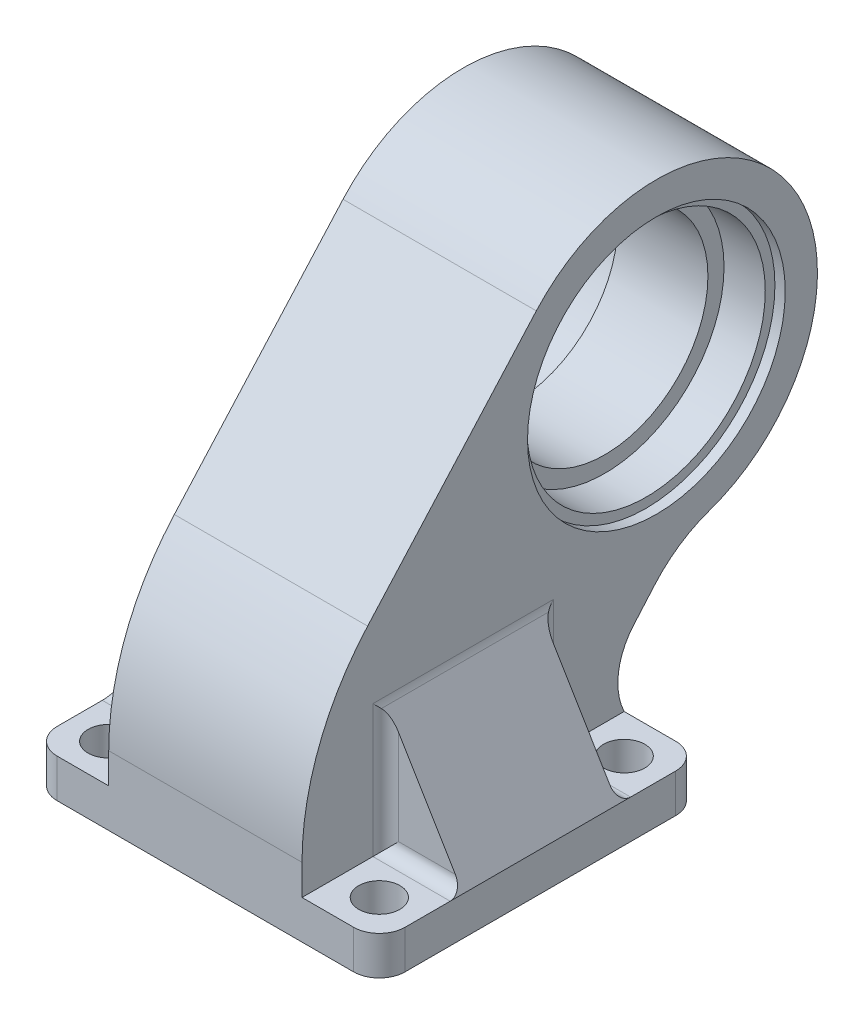
SolidWorks part; units mm, degrees
ref_plane "前视基准面" through (0, 0, 0) normal (0, 0, 1) x (1, 0, 0)
ref_plane "上视基准面" through (0, 0, 0) normal (0, 1, 0) x (1, 0, 0)
ref_plane "右视基准面" through (0, 0, 0) normal (1, 0, 0) x (0, 0, -1)
sketch "草图1" plane through (0, 0, 0) normal (0, 1, 0) x (1, 0, 0)
  line L1 (-13.5, -12.5) -> (13.5, -12.5)
  line L2 (-13.5, -12.5) -> (-13.5, 12.5)
  line L3 (-13.5, 12.5) -> (13.5, 12.5)
  line L4 (13.5, -12.5) -> (13.5, 12.5)
  line L5 (-13.5, -12.5) -> (13.5, 12.5) construction
  line L6 (-13.5, 12.5) -> (13.5, -12.5) construction
  point P0 (0, 0)
  dimension "D1" = 27
  dimension "D2" = 25
extrude "凸台-拉伸1" add sketch "草图1" along normal blind 3
sketch "草图2" plane through (0, 0, 0) normal (0, -1, 0) x (1, 0, 0)
  line L0 (0, 11.2561) -> (0, -9.0083) construction
  line L1 (-12.0564, 0) -> (11.3753, 0) construction
  circle A0 centre (-10.5, 9.5) radius 1.6
  circle A1 centre (-10.5, -9.5) radius 1.6
  circle A2 centre (10.5, -9.5) radius 1.6
  circle A3 centre (10.5, 9.5) radius 1.6
  dimension "D1" = 3.2
  dimension "D2" = 21
  dimension "D3" = 19
extrude "切除-拉伸1" cut sketch "草图2" against normal up to next
sketch "草图4" plane through (0, 0, 0) normal (1, 0, 0) x (0, 0, -1)
  line L0 (0, 0) -> (0, 12.2864) construction
  line L2 (-12.5, 3) -> (-12.5, 13)
  line L3 (-12.5, 13) -> (5.6822, 33.3324)
  line L4 (-12.5, 0) -> (12.5, 0) construction
  line L5 (12.5, 3) -> (24.4547, 16.8233)
  line L6 (-12.5, 3) -> (12.5, 3)
  circle A0 centre (15, 25) radius 12.5
  dimension "D1" = 25
  dimension "D3" = 25
  dimension "D2" = 15
  dimension "D4" = 10
extrude "圆孔位置" add sketch "草图4" along normal mid plane 15 contours A0 L3 L2 L6 L5 | A0 L2 region at (0, 11.7442, -1.1513) region at (0, 25, -15)
sketch "草图6" plane through (0, 0, 0) normal (0, 0, 1) x (1, 0, 0)
  line L0 (-13.5, 3) -> (-7.5, 3)
  line L1 (-7.5, 3) -> (-7.5, 13)
  line L2 (-7.5, 3) -> (-7.5, 13) construction
  line L3 (-7.5, 13) -> (-13.5, 3)
  line L4 (0, 0) -> (0, 24.773) construction
  line L5 (7.5, 3) -> (7.5, 13)
  line L6 (13.5, 3) -> (7.5, 3)
  line L7 (7.5, 13) -> (13.5, 3)
  dimension "D1" = 10
extrude "凸台-拉伸5" add sketch "草图6" along normal mid plane 12
sketch "草图7" plane through (7.5, 0, 0) normal (1, 0, 0) x (0, 0, -1)
  circle A0 centre (15, 25) radius 10
  dimension "D1" = 20
extrude "切除-拉伸3" cut sketch "草图7" against normal blind 0.8
sketch "草图8" plane through (7.5, 0, 0) normal (1, 0, 0) x (0, 0, -1)
  circle A0 centre (15, 25) radius 9.25
  dimension "D1" = 18.5
extrude "切除-拉伸4" cut sketch "草图8" against normal blind 4
sketch "草图9" plane through (7.5, 0, 0) normal (1, 0, 0) x (0, 0, -1)
  circle A0 centre (15, 25) radius 8
  dimension "D1" = 16
extrude "切除-拉伸5" cut sketch "草图9" against normal through all
mirror "镜向1" about plane through (0, 0, 0) normal (1, 0, 0) of "切除-拉伸4", "切除-拉伸3"
sketch "草图10" plane through (0, 0, 0) normal (0, -1, 0) x (1, 0, 0)
  circle A0 centre (0, 0) radius 9.25
  dimension "D1" = 18.5
extrude "切除-拉伸6" cut sketch "草图10" against normal blind 4.2
sketch "草图11" plane through (0, 0, 0) normal (0, -1, 0) x (1, 0, 0)
  circle A0 centre (0, 0) radius 7.5
  dimension "D1" = 15
extrude "切除-拉伸7" cut sketch "草图11" against normal blind 4.7
fillet "圆角1" radius 20 1 edges at (0, 13, 12.5)
sketch "草图12" plane through (7.5, 0, 0) normal (1, 0, 0) x (0, 0, -1)
  line L0 (12.5, 3) -> (10.2309, 4.9624)
  line L1 (10.2309, 4.9624) -> (16.8714, 12.6409)
  line L3 (12.5, 3) -> (24.4547, 16.8233) construction
  line L4 (12.5, 3) -> (24.4547, 16.8233)
  circle A0 centre (15, 25) radius 12.5
  line M11 (12.5, 3) -> (24.4547, 16.8233)
  dimension "D1" = 25
  dimension "D2" = 3
extrude "切除-拉伸8" cut sketch "草图12" against normal through all contours A0 L1 L0 M11 region at (7.5, 8.8141, -15.7108)
fillet "圆角2" radius 5 1 edges at (0, 4.9624, -10.2309)
fillet "圆角4" radius 10 1 edges at (0, 12.6409, -16.8714)
fillet "圆角5" radius 1 10 edges at (-10.5, 3, -6) (-7.5, 8, -6) (-7.5, 8, 6) (-10.5, 3, 6) (7.5, 8, -6) (10.5, 3, -6) (10.5, 3, 6) (7.5, 8, 6) (7.5, 13, 0) (-7.5, 13, 0)
fillet "圆角6" radius 2 4 edges at (13.5, 1.5, -12.5) (13.5, 1.5, 12.5) (-13.5, 1.5, 12.5) (-13.5, 1.5, -12.5)
